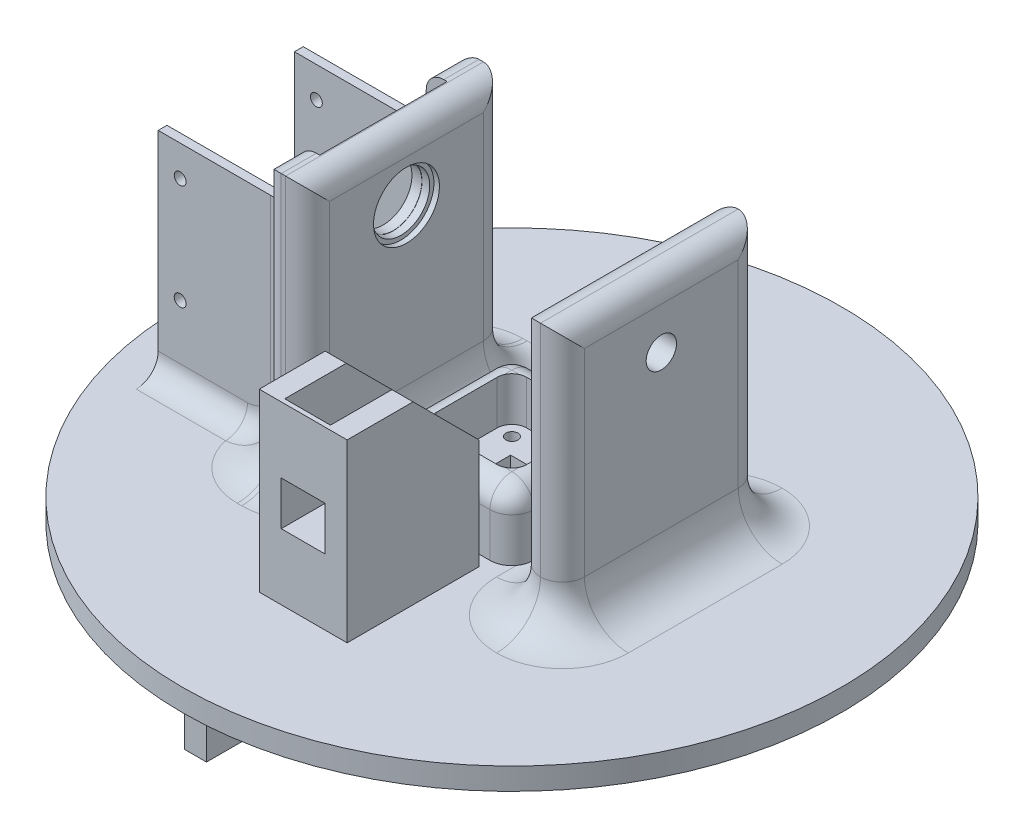
SolidWorks part; units mm, degrees
ref_plane "Plan de face" through (0, 0, 0) normal (0, 0, 1) x (1, 0, 0)
ref_plane "Plan de dessus" through (0, 0, 0) normal (0, 1, 0) x (1, 0, 0)
ref_plane "Plan de droite" through (0, 0, 0) normal (1, 0, 0) x (0, 0, -1)
sketch "Esquisse1" plane through (0, 0, 0) normal (0, 1, 0) x (1, 0, 0)
  circle A0 centre (0, 0) radius 46
  dimension "D1" = 92
extrude "Boss.-Extru.1" add sketch "Esquisse1" along normal blind 5
sketch "Esquisse4" plane through (0, 5, 0) normal (0, 1, 0) x (1, 0, 0)
  circle A0 centre (0, 0) radius 75
  dimension "D1" = 150
extrude "Boss.-Extru.2" add sketch "Esquisse4" along normal blind 5
sketch "Esquisse5" plane through (0, 10, 0) normal (0, 1, 0) x (1, 0, 0)
  line L1 (-34, -22.5) -> (34, -22.5)
  line L2 (-34, -22.5) -> (-34, 22.5)
  line L3 (-34, 22.5) -> (34, 22.5)
  line L4 (34, -22.5) -> (34, 22.5)
  line L5 (-34, -22.5) -> (34, 22.5) construction
  line L6 (-34, 22.5) -> (34, -22.5) construction
  point P0 (0, 0)
  dimension "D1" = 68
  dimension "D2" = 45
extrude "Boss.-Extru.3" add sketch "Esquisse5" along normal blind 60
sketch "Esquisse6" plane through (0, 0, 22.5) normal (0, 0, 1) x (1, 0, 0)
  line L0 (-34, 70) -> (34, 70) construction
  line L1 (-24, 70) -> (24, 70)
  line L2 (-24, 70) -> (-24, 10)
  line L3 (-24, 10) -> (24, 10)
  line L4 (24, 70) -> (24, 10)
  line L5 (-34, 10) -> (34, 10) construction
  line L6 (-34, 70) -> (-34, 10) construction
  dimension "D1" = 48
  dimension "D2" = 10
extrude "Enlèv. mat.-Extru.1" cut sketch "Esquisse6" against normal through all
sketch "Esquisse7" plane through (-34, 0, 0) normal (-1, 0, 0) x (0, 0, 1)
  line L0 (-22.5, 70) -> (22.5, 70) construction
  line L1 (-14.5, 68) -> (14.5, 68)
  line L2 (-14.5, 68) -> (-14.5, 20.5)
  line L3 (-14.5, 20.5) -> (14.5, 20.5)
  line L4 (14.5, 68) -> (14.5, 20.5)
  line L5 (-22.5, 70) -> (-22.5, 10) construction
  dimension "D1" = 29
  dimension "D2" = 47.5
  dimension "D3" = 2
  dimension "D4" = 8
extrude "Enlèv. mat.-Extru.2" cut sketch "Esquisse7" against normal blind 4.75
sketch "Esquisse8" plane through (-34, 0, 0) normal (-1, 0, 0) x (0, 0, 1)
  line L0 (-22.5, 10) -> (22.5, 10) construction
  line L1 (-16.5, 10) -> (-14.5, 10)
  line L2 (-16.5, 10) -> (-16.5, 58.5)
  line L3 (-16.5, 58.5) -> (-14.5, 58.5)
  line L4 (-14.5, 10) -> (-14.5, 58.5)
  line L5 (-14.5, 68) -> (-14.5, 20.5) construction
  line L6 (14.5, 20.5) -> (14.5, 68) construction
  line L7 (16.5, 10) -> (14.5, 10)
  line L8 (16.5, 10) -> (16.5, 58.5)
  line L9 (16.5, 58.5) -> (14.5, 58.5)
  line L10 (14.5, 10) -> (14.5, 58.5)
  line L11 (14.5, 68) -> (-14.5, 68) construction
  dimension "D1" = 2
  dimension "D2" = 2
  dimension "D3" = 9.5
  dimension "D4" = 9.5
extrude "Boss.-Extru.4" add sketch "Esquisse8" along normal blind 30
sketch "Esquisse9" plane through (-29.25, 0, 0) normal (-1, 0, 0) x (0, 0, 1)
  line L0 (14.5, 20.5) -> (14.5, 68) construction
  line L2 (-14.5, 20.5) -> (14.5, 20.5) construction
  circle A0 centre (0, 55.5) radius 3.45
  dimension "D1" = 6.9
  dimension "D2" = 14.5
  dimension "D3" = 35
extrude "Enlèv. mat.-Extru.3" cut sketch "Esquisse9" against normal through all
sketch "Esquisse11" plane through (-24, 0, 0) normal (1, 0, 0) x (0, 0, -1)
  circle A0 centre (0, 55.5) radius 6.55
  dimension "D1" = 13.1
extrude "Enlèv. mat.-Extru.5" cut sketch "Esquisse11" against normal blind 3
sketch "Esquisse12" plane through (-24, 0, 0) normal (1, 0, 0) x (0, 0, -1)
  circle A0 centre (0, 55.5) radius 7.5
  dimension "D1" = 15
extrude "Enlèv. mat.-Extru.6" cut sketch "Esquisse12" against normal blind 1.25
sketch "Esquisse13" plane through (24, 0, 0) normal (-1, 0, 0) x (0, 0, 1)
  circle A0 centre (0, 55.5) radius 6.55
  dimension "D1" = 13.1
extrude "Enlèv. mat.-Extru.7" cut sketch "Esquisse13" against normal blind 4
sketch "Esquisse14" plane through (24, 0, 0) normal (-1, 0, 0) x (0, 0, 1)
  circle A0 centre (0, 55.5) radius 7.5
  dimension "D1" = 15
extrude "Enlèv. mat.-Extru.8" cut sketch "Esquisse14" against normal blind 1.25
fillet "Congé1" radius 5 6 edges at (24, 40, 22.5) (24, 70, 0) (24, 40, -22.5) (-24, 40, -22.5) (-24, 70, 0) (-24, 40, 22.5)
fillet "Congé2" radius 5 3 edges at (34, 40, -22.5) (34, 70, 0) (34, 40, 22.5)
fillet "Congé3" radius 4 3 edges at (-34, 40, -22.5) (-34, 70, 0) (-34, 40, 22.5)
fillet "Congé5" radius 10 15 edges at (-32.8284, 10, -21.3284) (-29.5, 10, -22.5) (-25.4645, 10, -21.0355) (-32.8284, 10, 21.3284) (-29.5, 10, 22.5) (-25.4645, 10, 21.0355) (32.5355, 10, 21.0355) (25.4645, 10, 21.0355) (25.4645, 10, -21.0355) (32.5355, 10, -21.0355) (-24, 10, 0) (24, 10, 0) (34, 10, 0) (-34, 10, -17.5) (-34, 10, 17.5)
sketch "Esquisse15" plane through (0, 0, 0) normal (0, -1, 0) x (1, 0, 0)
  line L0 (-3.4, 0) -> (-3.4, -3.1)
  line L1 (-3.4, -3.1) -> (3.4, -3.1)
  line L2 (3.4, -3.1) -> (3.4, 0)
  arc A0 (3.4, 0) -> (-3.4, 0) centre (0, 0) ccw
  dimension "D1" = 3.4
  dimension "D2" = 3.1
extrude "Enlèv. mat.-Extru.9" cut sketch "Esquisse15" against normal through all both and the other way through all
sketch "Esquisse17" plane through (0, 10, 0) normal (0, 1, 0) x (1, 0, 0)
  line L1 (-15, -15) -> (15, -15)
  line L2 (-15, -15) -> (-15, 15)
  line L3 (-15, 15) -> (15, 15)
  line L4 (15, -15) -> (15, 15)
  line L5 (-15, -15) -> (15, 15) construction
  line L6 (-15, 15) -> (15, -15) construction
  point P0 (0, 0)
  dimension "D1" = 30
  dimension "D2" = 30
extrude "Boss.-Extru.5" add sketch "Esquisse17" along normal blind 15
sketch "Esquisse19" plane through (0, 10, 0) normal (0, -1, 0) x (1, 0, 0)
  line L0 (3.4, 0) -> (3.4, -3.1)
  line L1 (3.4, -3.1) -> (-3.4, -3.1) construction
  line L2 (3.4, -3.1) -> (-3.4, -3.1) construction
  line L3 (3.4, -3.1) -> (-3.4, -3.1)
  line L4 (-3.4, -3.1) -> (-3.4, 0)
  arc A0 (-3.4, 0) -> (3.4, 0) centre (0, 0) cw
extrude "Enlèv. mat.-Extru.11" cut sketch "Esquisse19" against normal through all
sketch "Esquisse23" plane through (0, 10, 0) normal (0, 1, 0) x (1, 0, 0)
  line L1 (-10, -17.5) -> (10, -17.5)
  line L2 (-10, -17.5) -> (-10, -47.5)
  line L3 (-10, -47.5) -> (10, -47.5)
  line L4 (10, -17.5) -> (10, -47.5)
  point P5 (0, -17.5)
  dimension "D1" = 30
  dimension "D2" = 20
  dimension "D3" = 17.5
extrude "Boss.-Extru.11" add sketch "Esquisse23" along normal blind 40 separate body
sketch "Esquisse24" plane through (0, 0, 0) normal (1, 0, 0) x (0, 0, -1)
  line L0 (-46.5, 40) -> (-24.1084, 18.6417)
  line L2 (-24.1084, 18.6417) -> (3.4924, 47.5778)
  line L3 (3.4924, 47.5778) -> (-18.2157, 68.2843)
  line L6 (-47.5, 50) -> (-17.5, 50) construction
  line L7 (-47.5, 50) -> (-47.5, 10) construction
  line L8 (-46.5, 40) -> (-46.5, 68.2843)
  line L9 (-46.5, 68.2843) -> (-18.2157, 68.2843)
  dimension "D1" = 40
  dimension "D2" = 30
  dimension "D3" = 10
  dimension "D4" = 1
  dimension "D5" = 28.2843
  dimension "D6" = 133.647
extrude "Enlèv. mat.-Extru.21" cut sketch "Esquisse24" against normal blind 5.2 and the other way blind 5.2
sketch "Esquisse25" plane through (0, 0, 0) normal (1, 0, 0) x (0, 0, -1)
  line L0 (-32.5, 50) -> (-17.5, 35)
  line L1 (-47.5, 50) -> (-17.5, 50) construction
  line L2 (-17.5, 65) -> (-17.5, 20) construction
  line L3 (-17.5, 35) -> (-17.5, 50)
  line L4 (-17.5, 50) -> (-32.5, 50)
  dimension "D1" = 45
extrude "Enlèv. mat.-Extru.22" cut sketch "Esquisse25" against normal blind 22.5 and the other way blind 22.5
sketch "Esquisse26" plane through (0, 0, 47.5) normal (0, 0, 1) x (1, 0, 0)
  line L0 (-10, 10) -> (10, 10) construction
  line L1 (-5, 35) -> (5, 35)
  line L2 (-5, 35) -> (-5, 25)
  line L3 (-5, 25) -> (5, 25)
  line L4 (5, 35) -> (5, 25)
  line L5 (-10, 50) -> (-10, 10) construction
  dimension "D1" = 15
  dimension "D2" = 10
  dimension "D3" = 5
  dimension "D4" = 10
extrude "Enlèv. mat.-Extru.23" cut sketch "Esquisse26" against normal blind 22.5
sketch "Esquisse27" plane through (0, 5, 0) normal (0, -1, 0) x (1, 0, 0)
  circle A1 centre (0, 0) radius 53
  circle A3 centre (0, 0) radius 50.55
  dimension "D1" = 101.1
  dimension "D2" = 106
extrude "Boss.-Extru.12" add sketch "Esquisse27" along normal blind 10
sketch "Esquisse28" plane through (0, 5, 0) normal (0, -1, 0) x (1, 0, 0)
  line L1 (-2.5, 72) -> (2.5, 72)
  line L2 (-2.5, 72) -> (-2.5, 52)
  line L3 (-2.5, 52) -> (2.5, 52)
  line L4 (2.5, 72) -> (2.5, 52)
  point P4 (0, 52)
  dimension "D1" = 20
  dimension "D2" = 5
  dimension "D3" = 52
extrude "Boss.-Extru.13" add sketch "Esquisse28" along normal blind 10
fillet "Congé7" radius 5 6 edges at (-34, 39.25, 16.5) (-36.9289, 12.9289, 16.5) (-34, 39.25, -16.5) (-36.9289, 12.9289, -16.5) (-54, 10, 16.5) (-54, 10, -16.5)
sketch "Esquisse31" plane through (0, 0, -16.5) normal (0, 0, -1) x (-1, 0, 0)
  line L0 (64, 58.5) -> (38.4853, 58.5) construction
  line L1 (64, 58.5) -> (64, 15) construction
  circle A0 centre (59, 51.5) radius 1.35
  circle A1 centre (59, 27.5) radius 1.35
  dimension "D1" = 2.7
  dimension "D2" = 7
  dimension "D3" = 5
  dimension "D4" = 24
extrude "Enlèv. mat.-Extru.24" cut sketch "Esquisse31" against normal through all
fillet "Congé11" radius 5 2 edges at (-15, 25, 0) (15, 25, 0)
fillet "Congé12" radius 5 5 edges at (15, 15.0251, -15) (13.5355, 23.5355, -15) (-15, 15.0251, -15) (-13.5355, 23.5355, -15) (0, 25, -15)
fillet "Congé13" radius 5 5 edges at (-15, 15.0251, 15) (-13.5355, 23.5355, 15) (15, 15.0251, 15) (13.5355, 23.5355, 15) (0, 25, 15)
sketch "Esquisse32" plane through (0, 68, 0) normal (0, -1, 0) x (1, 0, 0)
  line L1 (-34, -14.5) -> (-29.25, -14.5)
  line L2 (-34, -14.5) -> (-34, 14.5)
  line L3 (-34, 14.5) -> (-29.25, 14.5)
  line L4 (-29.25, -14.5) -> (-29.25, 14.5)
  line L5 (-64, 14.5) -> (-34, 14.5) construction
  dimension "D1" = 4.75
extrude "Enlèv. mat.-Extru.25" cut sketch "Esquisse32" against normal blind 10
sketch "Esquisse33" plane through (-29.25, 0, 0) normal (-1, 0, 0) x (0, 0, 1)
  circle A0 centre (0, 55.5) radius 6.5
  dimension "D1" = 13
extrude "Enlèv. mat.-Extru.27" cut sketch "Esquisse33" against normal blind 10
sketch "Esquisse34" plane through (0, 25, 0) normal (0, 1, 0) x (1, 0, 0)
  line L0 (-10.285, 6.915) -> (-10.285, -6.915)
  line L5 (-6.915, 10.285) -> (6.915, 10.285)
  line L6 (10.285, 6.915) -> (10.285, -6.915)
  line L7 (6.915, -10.285) -> (-6.915, -10.285)
  line L8 (15, -10) -> (15, 10) construction
  line L9 (10, 15) -> (-10, 15) construction
  line L10 (-15, 10) -> (-15, -10) construction
  line L11 (-10, -15) -> (10, -15) construction
  arc A0 (-6.915, 10.285) -> (-10.285, 6.915) centre (-6.915, 6.915) ccw
  arc A1 (10.285, 6.915) -> (6.915, 10.285) centre (6.915, 6.915) ccw
  arc A2 (-10.285, -6.915) -> (-6.915, -10.285) centre (-6.915, -6.915) ccw
  arc A3 (6.915, -10.285) -> (10.285, -6.915) centre (6.915, -6.915) ccw
  point P7 (0, 10.285)
  point P8 (10.285, 0)
  dimension "D3" = 6.74
  dimension "D4" = 6.74
  dimension "D5" = 6.74
  dimension "D6" = 6.74
  dimension "D1" = 13.83
  dimension "D2" = 13.83
extrude "Enlèv. mat.-Extru.28" cut sketch "Esquisse34" against normal blind 10
sketch "Esquisse35" plane through (0, 0, -15) normal (0, 0, -1) x (-1, 0, 0)
  line L0 (-5, 25) -> (-5, 20)
  line L1 (5, 20) -> (5, 25)
  line L2 (5, 25) -> (-5, 25)
  line L3 (-10, 25) -> (-8.2713, 25) construction
  arc A0 (-5, 20) -> (5, 20) centre (0, 20) ccw
  point P7 (0, 25)
  dimension "D1" = 5
  dimension "D2" = 5
extrude "Enlèv. mat.-Extru.29" cut sketch "Esquisse35" against normal blind 10
sketch "Esquisse38" plane through (0, 15, 0) normal (0, 1, 0) x (1, 0, 0)
  line L0 (-6.915, 6.915) -> (6.915, 6.915) construction
  line L1 (6.915, 6.915) -> (6.915, -6.915) construction
  line L2 (6.915, -6.915) -> (-6.915, -6.915) construction
  line L3 (-6.915, -6.915) -> (-6.915, 6.915) construction
  line L4 (-5, 10.285) -> (-6.915, 10.285) construction
  line L5 (10.285, -6.915) -> (10.285, 6.915) construction
  line L6 (-6.915, -10.285) -> (6.915, -10.285) construction
  line L7 (-10.285, 6.915) -> (-10.285, -6.915) construction
  dimension "D1" = 3.37
  dimension "3.37" = 3.37
  dimension "D2" = 3.37
  dimension "D3" = 3.37
hole_wizard "Chambrage pour vis à tête ronde bombée M21" positions "Esquisse40" profile "Esquisse41" counterbore size "M2" standard "Ansi Metric" end condition through all
sketch "Esquisse40" plane through (0, 0, 0) normal (0, -1, 0) x (-1, 0, 0)
  point P0 (6.915, 6.915)
  point P3 (6.915, -6.915)
  point P6 (-6.915, -6.915)
  point P9 (-6.915, 6.915)
sketch "Esquisse41" plane through (-6.915, 0, -6.915) normal (1, 0, 0) x (0, 0, -1)
  line L0 (0, 0) -> (0, 70)
  line L1 (0, 70) -> (1.375, 70)
  line L3 (1.375, 70) -> (1.375, 5)
  line L4 (1.375, 5) -> (3.5, 5)
  line L5 (3.5, 5) -> (3.5, 0)
  line L7 (3.5, 0) -> (0, 0)
  line L11 (0, -6.35) -> (0, 107.95) construction
  dimension "Diamètre du perçage jusqu'au prochain" = 2.75
  dimension "Profondeur du perçage jusqu'au prochain" = 70
  dimension "Diamètre du chambrage" = 7
  dimension "Profondeur du chambrage" = 5
